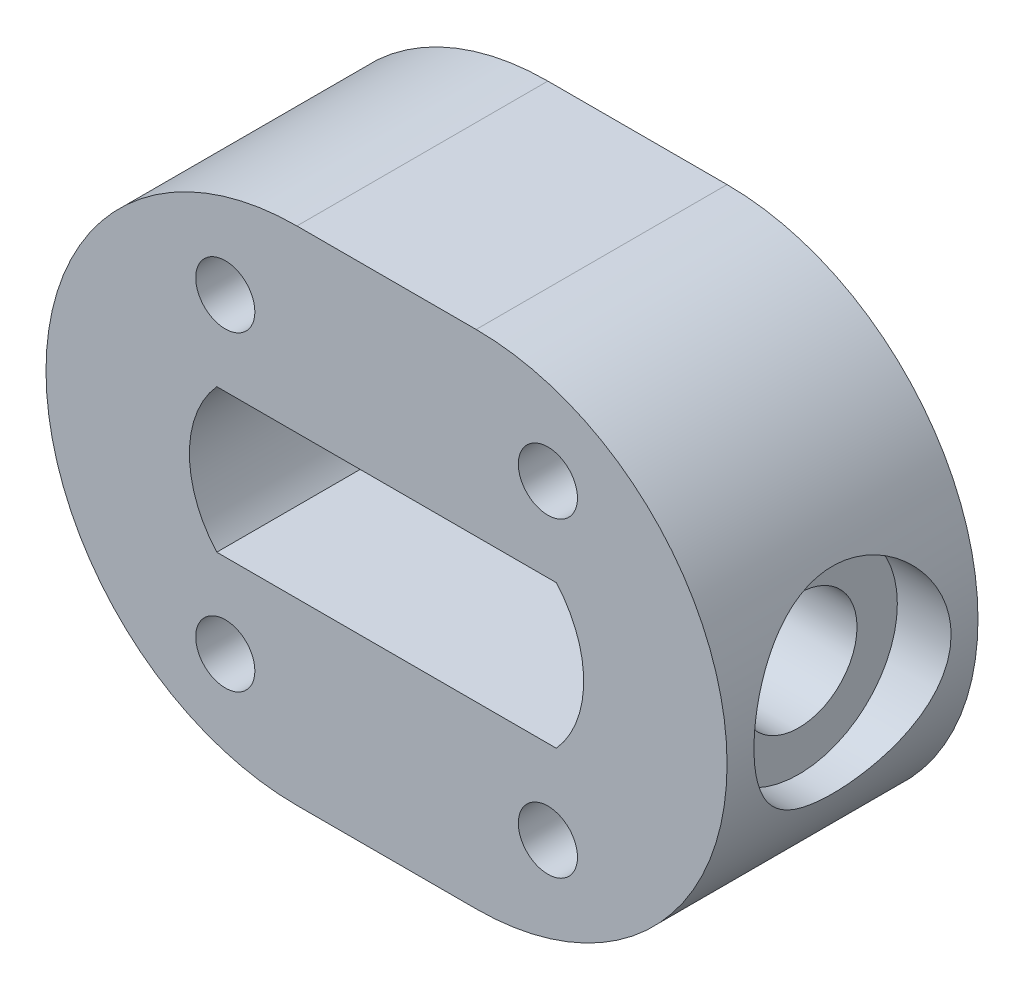
SolidWorks part; units mm, degrees
ref_plane "Front Plane" through (0, 0, 0) normal (0, 0, 1) x (1, 0, 0)
ref_plane "Top Plane" through (0, 0, 0) normal (0, 1, 0) x (1, 0, 0)
ref_plane "Right Plane" through (0, 0, 0) normal (1, 0, 0) x (0, 0, -1)
sketch "Sketch1" plane through (0, 0, 0) normal (0, 0, 1) x (1, 0, 0)
  line L0 (0, 0) -> (10, 0) construction
  line L1 (0, 14) -> (10, 14)
  line L2 (0, -14) -> (10, -14)
  line L3 (0, 0) -> (10, 0) construction
  line L6 (-4.4721, 4) -> (14.4721, 4)
  line L7 (-4.4721, -4) -> (14.4721, -4)
  arc A0 (0, 14) -> (0, -14) centre (0, 0) ccw
  arc A1 (10, -14) -> (10, 14) centre (10, 0) ccw
  arc A3 (-4.4721, 4) -> (-4.4721, -4) centre (0, 0) ccw
  arc A4 (14.4721, -4) -> (14.4721, 4) centre (10, 0) ccw
  point P3 (5, 0)
  point P12 (5, 0)
  dimension "D1" = 14
  dimension "D2" = 10
  dimension "D3" = 8
  dimension "D4" = 6
  dimension "D5" = 4
  dimension "D6" = 6
extrude "Boss-Extrude1" add sketch "Sketch1" along normal blind 14
sketch "Sketch2" plane through (0, 0, 14) normal (0, 0, 1) x (1, 0, 0)
  line L0 (0, 0) -> (10, 0) construction
  line L1 (5.0031, 0) -> (5.0031, 3.2311) construction
  circle A0 centre (5.0031, 0) radius 12.5 construction
  point P7 (-3.9969, 8.6747)
  point P16 (14.0031, 8.6747)
  point P17 (-3.9969, -8.6747)
  point P18 (14.0031, -8.6747)
  dimension "D1" = 25
  dimension "D2" = 8.6747
  dimension "D4" = 9
hole_wizard "M4 Tapped Hole2" positions "3DSketch2" profile "Sketch4" tap size "M4" standard "ISO" end condition through all
sketch3d "3DSketch2"
  point P0 (-3.9969, 8.6747, 14)
  point P3 (14.0031, 8.6747, 14)
  point P6 (14.0031, -8.6747, 14)
  point P9 (-3.9969, -8.6747, 14)
sketch "Sketch4" plane through (-3.9969, 8.6747, 14) normal (1, 0, 0) x (0, -1, 0)
  line L0 (0, 0) -> (0, 14)
  line L1 (0, 14) -> (1.65, 14)
  line L2 (1.65, 14) -> (1.65, 0)
  line L5 (1.65, 0) -> (0, 0)
  line L11 (0, -6.35) -> (0, 107.95) construction
  dimension "Thru Tap Drill Dia." = 3.3
  dimension "Thru Tap Drill Depth" = 14
cosmetic thread "Hole Thread5" parameters "D2"=4
cosmetic thread "Hole Thread6" parameters "D2"=4
cosmetic thread "Hole Thread7" parameters "D2"=4
cosmetic thread "Hole Thread8" parameters "D2"=4
ref_plane "Plane1" through (24, 0, 0) normal (1, 0, 0) x (0, 0, -1)
sketch "Sketch5" plane through (24, 0, 0) normal (1, 0, 0) x (0, 0, -1)
  line L0 (-14, 14) -> (0, 14) construction
  line L1 (0, -14) -> (0, 14) construction
  circle A0 centre (-7, 0) radius 3.25
  dimension "D1" = 6.5
  dimension "D2" = 14
  dimension "D3" = 7
extrude "Cut-Extrude1" cut sketch "Sketch5" against normal up to surface (8 mm away) up to face at (15.2361, 0, 7)
sketch "Sketch6" plane through (24, 0, 0) normal (1, 0, 0) x (0, 0, -1)
  circle A0 centre (-7, 0) radius 5.5
  dimension "D1" = 11
extrude "Cut-Extrude2" cut sketch "Sketch6" against normal blind 3
